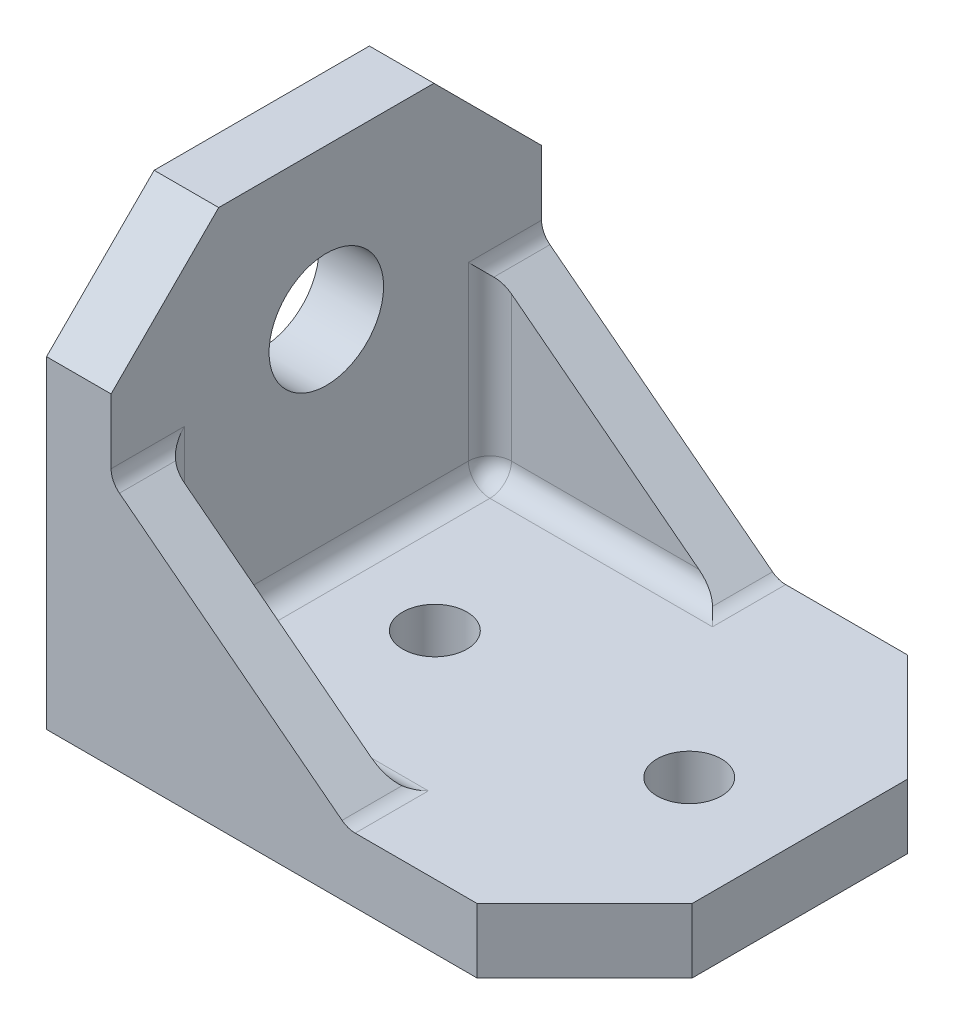
SolidWorks part; units mm, degrees
material "ABS"
ref_plane "Front" through (0, 0, 0) normal (0, 0, 1) x (1, 0, 0)
ref_plane "Top" through (0, 0, 0) normal (0, 1, 0) x (1, 0, 0)
ref_plane "Right" through (0, 0, 0) normal (1, 0, 0) x (0, 0, -1)
ref_axis "Axis1" through (0, 0, 55) along (0, 0, -1)
sketch "Sketch1" plane through (0, 0, 0) normal (0, 0, 1) x (1, 0, 0)
  line L0 (0, 0) -> (0, 25.4)
  line L1 (0, 0) -> (31.75, 0)
  line L2 (3.81, 3.81) -> (31.75, 3.81)
  line L3 (3.81, 3.81) -> (3.81, 25.4)
  line L4 (0, 25.4) -> (3.81, 25.4)
  line L5 (31.75, 3.81) -> (31.75, 0)
  dimension "D2" = 25.4
  dimension "D3" = 31.75
  dimension "D1" = 3.81
extrude "Boss-Extrude1" add sketch "Sketch1" along normal blind 25.4
hole_wizard "#6 Clearance Hole1" positions "Sketch2" profile "Sketch3" hole size "#6" standard "ANSI Inch" end condition through all
sketch "Sketch2" plane through (0, 3.81, 0) normal (0, 1, 0) x (1, 0, 0)
  line L0 (3.81, -12.7) -> (31.75, -12.7) construction
  line L1 (3.81, -25.4) -> (3.81, 0) construction
  line L2 (31.75, -25.4) -> (31.75, 0) construction
  line L4 (0, -25.4) -> (0, 0) construction
  point P0 (10.2108, -12.7)
  point P2 (25.2222, -12.7)
  dimension "D1" = 15.0114
  dimension "D2" = 10.2108
sketch "Sketch3" plane through (10.2108, 3.81, 12.7) normal (1, 0, 0) x (0, 0, 1)
  line L0 (0, 0) -> (0, 3.81)
  line L1 (0, 3.81) -> (1.8986, 3.81)
  line L2 (1.8986, 3.81) -> (1.8986, 0)
  line L5 (1.8986, 0) -> (0, 0)
  line L11 (0, -6.35) -> (0, 107.95) construction
  dimension "Thru Hole Dia." = 3.7973
  dimension "Thru Hole Depth" = 3.81
hole_wizard "1/4 Clearance Hole1" positions "Sketch4" profile "Sketch5" hole size "1/4" standard "ANSI Inch" end condition through all
sketch "Sketch4" plane through (3.81, 0, 0) normal (1, 0, 0) x (0, 0, -1)
  line L0 (-12.7, 25.4) -> (-12.7, 3.81) construction
  line L1 (-25.4, 25.4) -> (0, 25.4) construction
  line L2 (-25.4, 3.81) -> (0, 3.81) construction
  point P0 (-12.7, 16.51)
  dimension "D1" = 8.89
sketch "Sketch5" plane through (3.81, 16.51, 12.7) normal (0, 1, 0) x (0, 0, -1)
  line L0 (0, 0) -> (0, 3.81)
  line L1 (0, 3.81) -> (3.3782, 3.81)
  line L2 (3.3782, 3.81) -> (3.3782, 0)
  line L5 (3.3782, 0) -> (0, 0)
  line L11 (0, -6.35) -> (0, 107.95) construction
  dimension "Thru Hole Dia." = 6.7564
  dimension "Thru Hole Depth" = 3.81
sketch "Sketch6" plane through (0, 0, 25.4) normal (0, 0, 1) x (1, 0, 0)
  line L0 (3.81, 3.81) -> (17.78, 3.81)
  line L1 (31.75, 3.81) -> (3.81, 3.81) construction
  line L2 (17.78, 3.81) -> (3.81, 14.605)
  line L3 (3.81, 3.81) -> (3.81, 25.4) construction
  line L4 (3.81, 14.605) -> (3.81, 3.81)
extrude "Boss-Extrude2" add sketch "Sketch6" against normal blind 3.048
sketch "Sketch7" plane through (0, 0, 0) normal (0, 0, -1) x (-1, 0, 0)
  line L0 (-3.81, 3.81) -> (-17.78, 3.81)
  line L1 (-31.75, 3.81) -> (-3.81, 3.81) construction
  line L2 (-17.78, 3.81) -> (-3.81, 14.605)
  line L3 (-3.81, 3.81) -> (-3.81, 25.4) construction
  line L4 (-3.81, 14.605) -> (-3.81, 3.81)
extrude "Boss-Extrude3" add sketch "Sketch7" against normal blind 3.048
fillet "Fillet1" radius 1.27 9 edges at (17.78, 3.81, 23.876) (3.81, 14.605, 23.876) (3.81, 14.605, 1.524) (17.78, 3.81, 1.524) (10.795, 3.81, 22.352) (3.81, 9.2075, 22.352) (10.795, 3.81, 3.048) (3.81, 9.2075, 3.048) (3.81, 3.81, 12.7)
chamfer "Chamfer1" distance 6.35 angle 45 4 edges at (1.905, 25.4, 25.4) (1.905, 25.4, 0) (31.75, 1.905, 25.4) (31.75, 1.905, 0)
